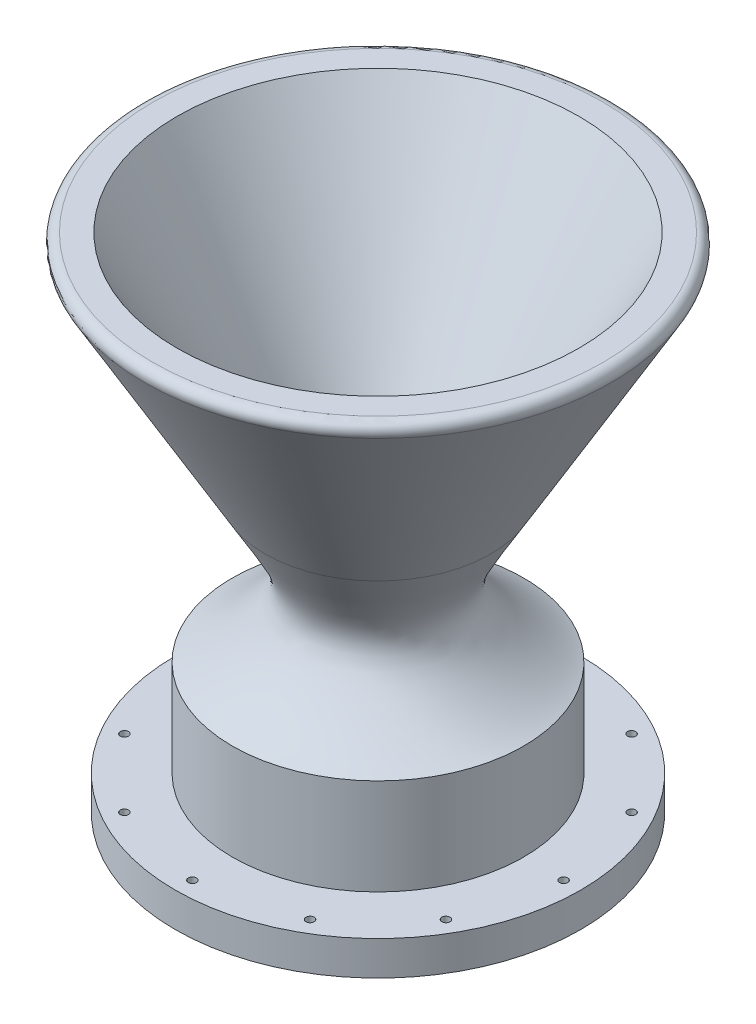
SolidWorks part; units mm, degrees
material "AISI 304"
ref_plane "Front Plane" through (0, 0, 0) normal (0, 0, 1) x (1, 0, 0)
ref_plane "Top Plane" through (0, 0, 0) normal (0, 1, 0) x (1, 0, 0)
ref_plane "Right Plane" through (0, 0, 0) normal (1, 0, 0) x (0, 0, -1)
sketch "Sketch2" plane through (0, 0, 0) normal (0, 0, 1) x (1, 0, 0)
  line L0 (0, 0) -> (56.388, 0)
  line L1 (56.388, 0) -> (56.388, 9.525)
  line L3 (6.35, 41.2962) -> (6.35, 53.9962)
  line L5 (25.493, 9.525) -> (89.279, 9.525) construction
  line L6 (-7.1602, 53.9962) -> (28.0549, 53.9962) construction
  line L7 (6.35, 53.9962) -> (55.88, 139.7846)
  line L9 (55.88, 139.7846) -> (62.656, 139.7846)
  line L10 (64.8557, 135.9746) -> (31.35, 77.9411)
  line L14 (6.35, 41.2962) -> (21.7805, 32.3874)
  line L15 (21.7805, 32.3874) -> (21.7805, 6.35)
  line L16 (21.7805, 6.35) -> (0, 6.35)
  line L17 (0, 6.35) -> (0, 0)
  line L18 (56.388, 9.525) -> (40.513, 9.525)
  line L19 (40.513, 9.525) -> (40.513, 36.2737)
  arc A0 (64.8557, 135.9746) -> (62.656, 139.7846) centre (62.656, 137.2446) ccw
  spline S0 degree 3 poles (31.35, 77.9411) (21.9947, 61.4956) (14.4962, 54.512) (35.0255, 38.6063) (40.513, 36.2737) knots 0 0 0 0 0.510149 0.739608 0.739608 0.739608 0.739608
  dimension "D4" = 2.54
  dimension "D1" = 56.388
  dimension "D2" = 9.525
  dimension "D3" = 60
  dimension "D5" = 12.7
  dimension "D6" = 6.35
  dimension "D7" = 15.875
revolve "Revolve1" add sketch "Sketch2" angle 360 about L17
sketch "Sketch5" plane through (0, 0, 0) normal (0, -1, 0) x (-1, 0, 0)
  point P0 (0, -51.6382)
  dimension "D1" = 51.6382
hole_wizard "Tap Drill for #4-40 Tap1" positions "3DSketch1" profile "Sketch6" hole size "#4-40" standard "ANSI Inch" end condition up to next
sketch3d "3DSketch1"
  point P0 (0, 0, 51.6382)
sketch "Sketch6" plane through (0, 0, 51.6382) normal (1, 0, 0) x (0, 0, -1)
  line L0 (0, 0) -> (0, 132.4376)
  line L1 (0, 132.4376) -> (1.1303, 132.4376)
  line L2 (1.1303, 132.4376) -> (1.1303, 0)
  line L5 (1.1303, 0) -> (0, 0)
  line L11 (0, -6.35) -> (0, 107.95) construction
  dimension "Thru Hole Dia." = 2.2606
  dimension "Thru Hole Depth" = 132.4376
pattern_circular "CirPattern2" count 12 over 360 about axis through (0, 0, 0) along (0, 1, 0) of "Tap Drill for #4-40 Tap1"
